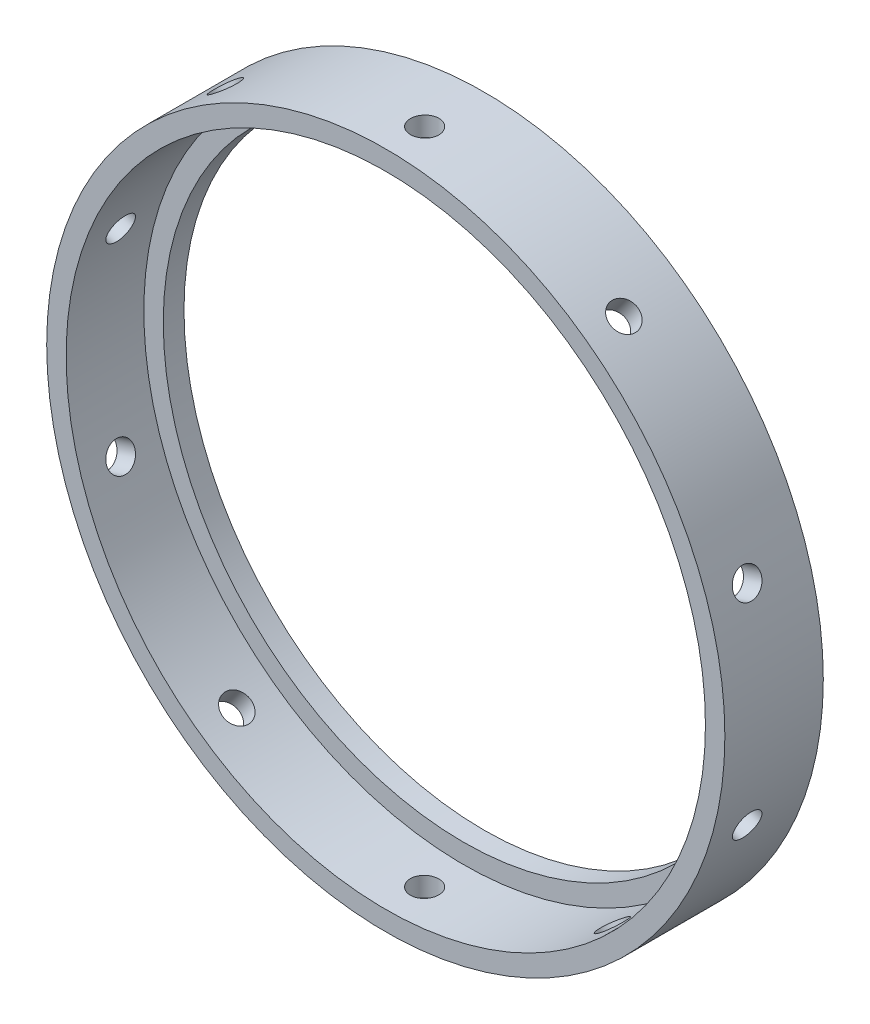
SolidWorks part; units mm, degrees
ref_plane "Front Plane" through (0, 0, 0) normal (0, 0, 1) x (1, 0, 0)
ref_plane "Top Plane" through (0, 0, 0) normal (0, 1, 0) x (1, 0, 0)
ref_plane "Right Plane" through (0, 0, 0) normal (1, 0, 0) x (0, 0, -1)
sketch "Sketch1" plane through (0, 0, 0) normal (0, 0, 1) x (1, 0, 0)
  circle A0 centre (0, 0) radius 78.359
  circle A1 centre (0, 0) radius 83.1215
  dimension "D1" = 156.718
  dimension "D2" = 166.243
extrude "Boss-Extrude1" add sketch "Sketch1" along normal blind 19.05
sketch "Sketch2" plane through (0, 0, 0) normal (0, 1, 0) x (1, 0, 0)
  line L0 (78.359, 0) -> (-78.359, 0) construction
  line L1 (0, -2.0807) -> (0, -15.8358) construction
  circle A0 centre (0, -9.525) radius 3.4782
  dimension "D1" = 9.525
extrude "Cut-Extrude1" cut sketch "Sketch2" against normal through all
ref_axis "Axis1" through (0, 0, 2.0807) along (0, 0, 1)
pattern_circular "CirPattern1" count 10 over 360 about axis through (0, 0, 2.0807) along (0, 0, 1) of "Cut-Extrude1"
sketch "Sketch3" plane through (0, 0, 0) normal (0, 0, -1) x (-1, 0, 0)
  circle A0 centre (0, 0) radius 83.1215
  circle A1 centre (0, 0) radius 73.5965
  dimension "D1" = 166.243
  dimension "D2" = 147.193
extrude "Boss-Extrude2" add sketch "Sketch3" along normal blind 5.08
